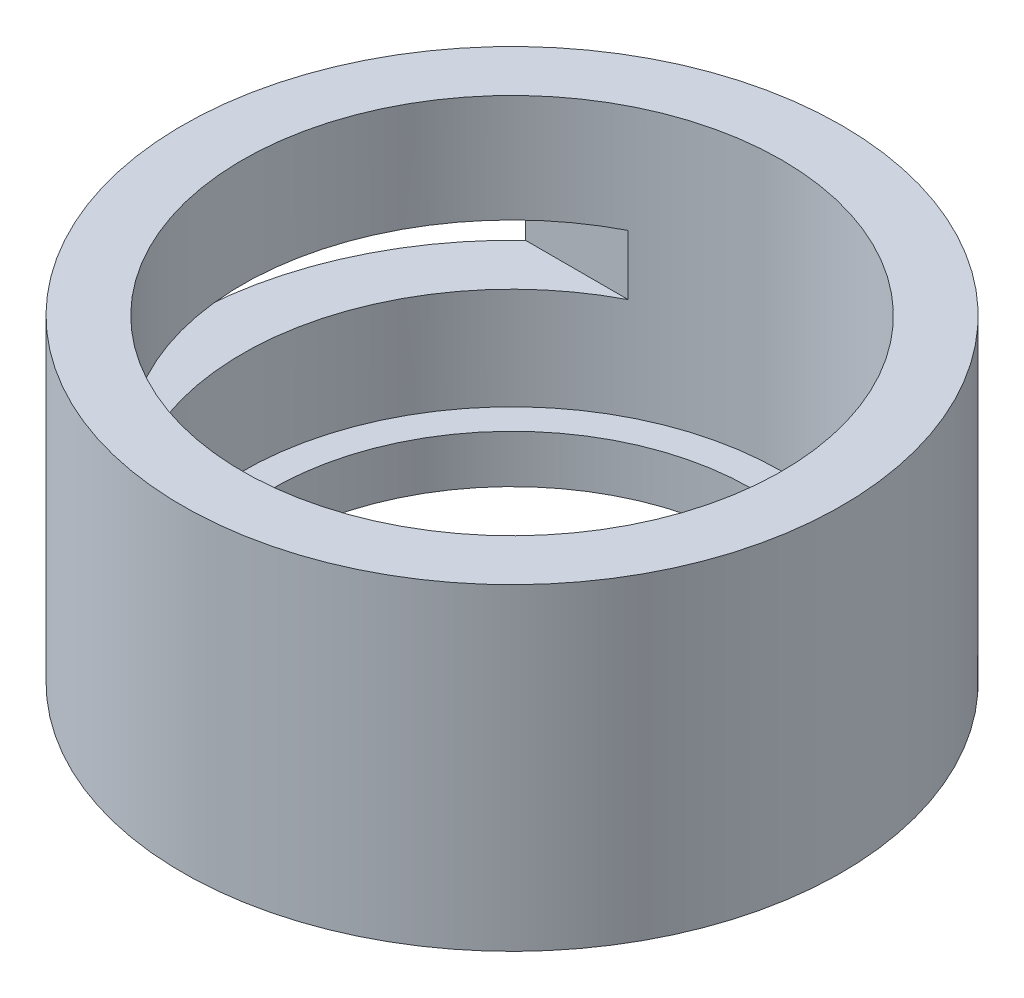
SolidWorks part; units mm, degrees
ref_plane "Front Plane" through (0, 0, 0) normal (0, 0, 1) x (1, 0, 0)
ref_plane "Top Plane" through (0, 0, 0) normal (0, 1, 0) x (1, 0, 0)
ref_plane "Right Plane" through (0, 0, 0) normal (1, 0, 0) x (0, 0, -1)
ref_axis "RotationAxis_J1_Base" through (0, 0, 0) along (0, 1, 0)
sketch "Sketch1" plane through (0, 0, 0) normal (0, 0, 1) x (1, 0, 0)
  line L7 (0, 0) -> (0, 58.2775) construction
  line L8 (0, 0) -> (0, 69.0457) construction
  line L10 (40, 7.9152) -> (55, 7.9152)
  line L11 (55, 7.9152) -> (55, 60.9152)
  line L12 (55, 60.9152) -> (45, 60.9152)
  line L13 (45, 60.9152) -> (45, 15.9152)
  line L14 (45, 15.9152) -> (40, 15.9152)
  line L15 (40, 15.9152) -> (40, 7.9152)
  dimension "D1" = 40
  dimension "D2" = 45
  dimension "D3" = 8
  dimension "D4" = 55
  dimension "D5" = 45
revolve "Revolve1" add sketch "Sketch1" angle 360 about L7
ref_plane "ContactPlane_J1_Base_Radiator" through (0, 15.9152, 0) normal (0, 1, 0) x (1, 0, 0)
ref_plane "GearOpeningPlane" through (-55, 0, 0) normal (-1, 0, 0) x (0, 0, 1)
sketch "Sketch2" plane through (-55, 0, 0) normal (-1, 0, 0) x (0, 0, 1)
  line L0 (0, 0) -> (0, 69.0457) construction
  line L1 (-40, 42.9152) -> (40, 42.9152)
  line L2 (-40, 42.9152) -> (-40, 32.9152)
  line L3 (-40, 32.9152) -> (40, 32.9152)
  line L4 (40, 42.9152) -> (40, 32.9152)
  line L6 (49.5, 15.9152) -> (-49.5, 15.9152) construction
  dimension "D1" = 10
  dimension "D2" = 80
  dimension "D3" = 40
  dimension "D4" = 17
extrude "Cut-Extrude1" cut sketch "Sketch2" against normal blind 39
equation "\"D2\"=80"
